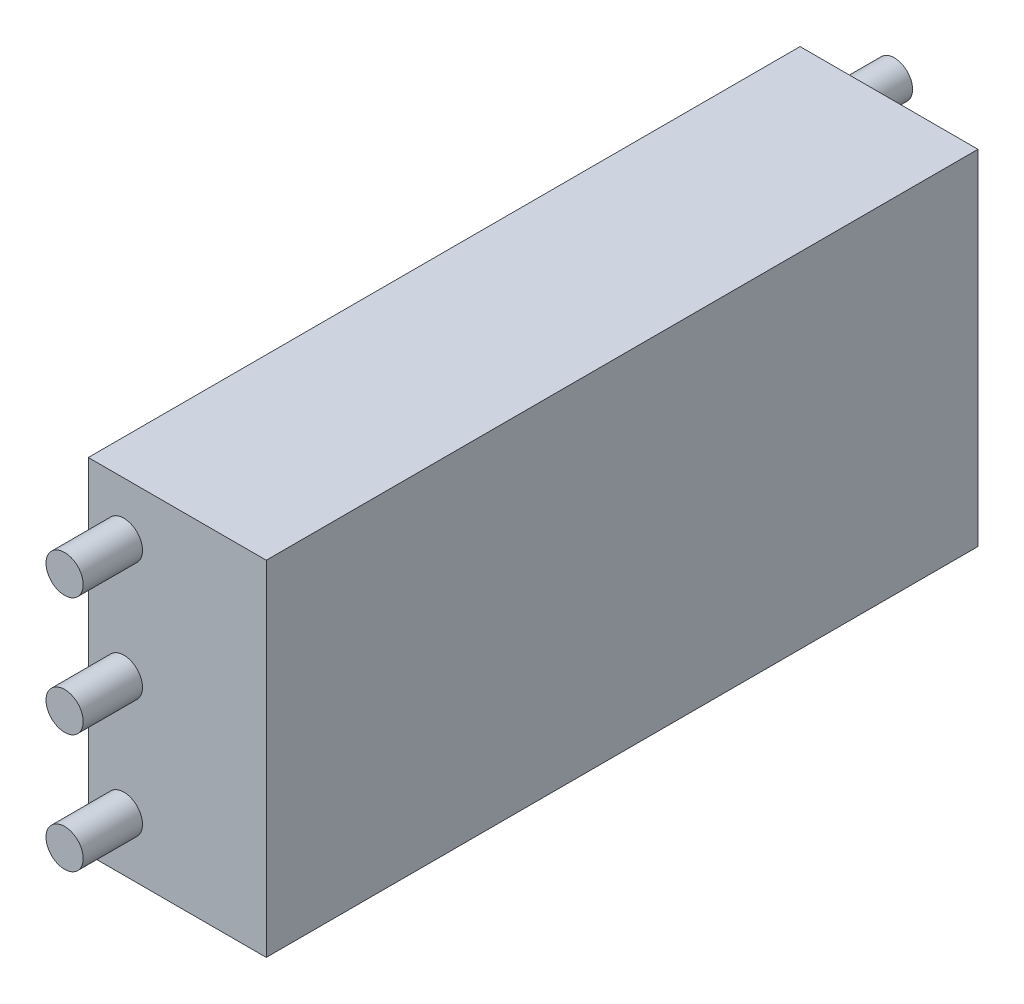
SolidWorks part; units mm, degrees
ref_plane "Front" through (0, 0, 0) normal (0, 0, 1) x (1, 0, 0)
ref_plane "Top" through (0, 0, 0) normal (0, 1, 0) x (1, 0, 0)
ref_plane "Right" through (0, 0, 0) normal (1, 0, 0) x (0, 0, -1)
sketch "Sketch1" plane through (0, 0, 0) normal (1, 0, 0) x (0, 0, -1)
  line L1 (0, 0) -> (60, 0)
  line L2 (0, 0) -> (0, 29)
  line L3 (0, 29) -> (60, 29)
  line L4 (60, 0) -> (60, 29)
  dimension "D1" = 29
  dimension "D2" = 60
extrude "Boss-Extrude1" add sketch "Sketch1" along normal blind 15
sketch "Sketch2" plane through (0, 0, 0) normal (0, 0, 1) x (1, 0, 0)
  line L0 (3, 24.5) -> (3, 4.5) construction
  line L1 (0, 29) -> (0, 0) construction
  circle A0 centre (3, 24.5) radius 1.5674
  circle A1 centre (3, 14.5) radius 1.5674
  circle A2 centre (3, 4.5) radius 1.5674
  point P2 (3, 14.5)
  point P7 (3.291, 26.4742)
  point P8 (0, 0)
  point P11 (0, 14.5)
  dimension "D1" = 20
  dimension "D2" = 3
extrude "Boss-Extrude2" add sketch "Sketch2" along normal blind 5
sketch "Sketch3" plane through (0, 0, -60) normal (0, 0, -1) x (-1, 0, 0)
  circle A0 centre (-2.9474, 25.6152) radius 1.5394
  circle A1 centre (-2.9474, 3.4192) radius 1.5394
  point P4 (0, 0)
  point P5 (-4.2531, 4.9997)
  point P6 (-3.8751, 23.7941)
  point P7 (-3.2223, 25.6152)
  point P8 (-2.9474, 3.4192)
extrude "Boss-Extrude3" add sketch "Sketch3" along normal blind 5
